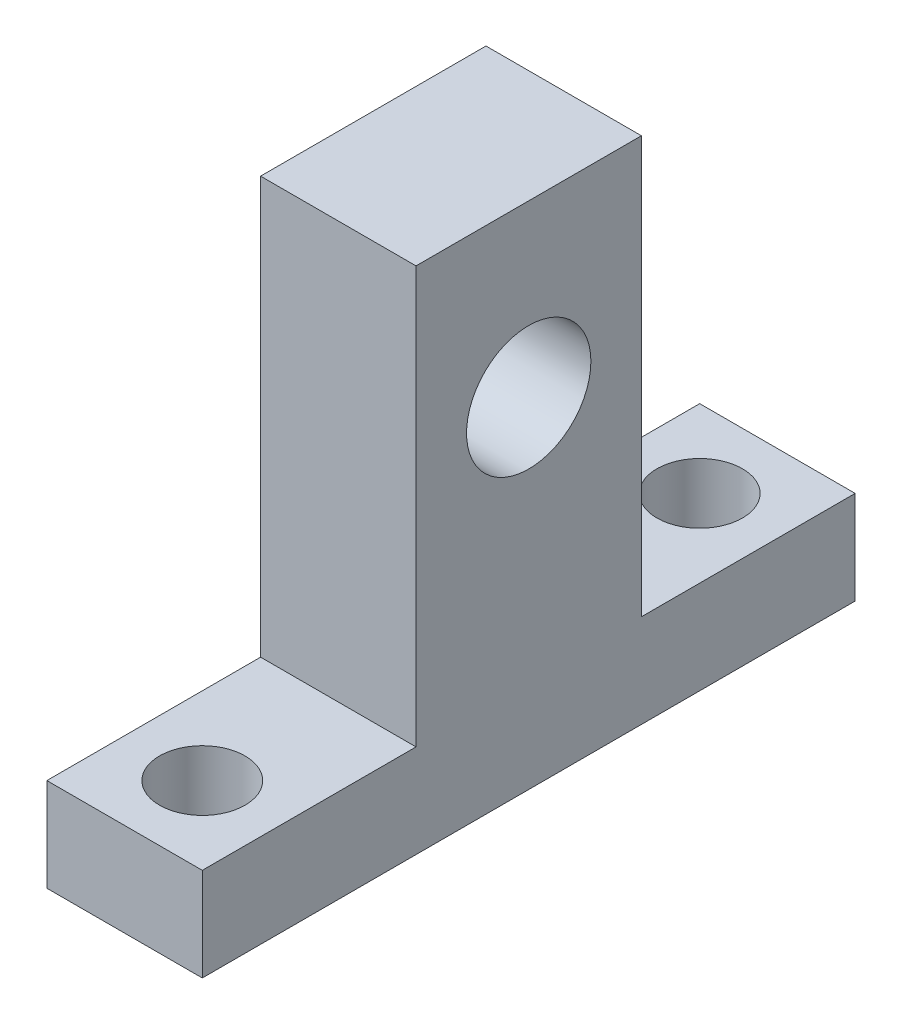
SolidWorks part; units mm, degrees
ref_plane "Front Plane" through (0, 0, 0) normal (0, 0, 1) x (1, 0, 0)
ref_plane "Top Plane" through (0, 0, 0) normal (0, 1, 0) x (1, 0, 0)
ref_plane "Right Plane" through (0, 0, 0) normal (1, 0, 0) x (0, 0, -1)
sketch "Sketch1" plane through (0, 0, 0) normal (0, 1, 0) x (1, 0, 0)
  line L1 (-5, 21) -> (5, 21)
  line L2 (-5, 21) -> (-5, -21)
  line L3 (-5, -21) -> (5, -21)
  line L4 (5, 21) -> (5, -21)
  line L5 (-5, 21) -> (5, -21) construction
  line L6 (-5, -21) -> (5, 21) construction
  line L7 (-5, 7.25) -> (5, 7.25)
  line L8 (-5, 7.25) -> (-5, -7.25)
  line L9 (-5, -7.25) -> (5, -7.25)
  line L10 (5, 7.25) -> (5, -7.25)
  line L11 (-5, 7.25) -> (5, -7.25) construction
  line L12 (-5, -7.25) -> (5, 7.25) construction
  circle A0 centre (0, 16) radius 2.75
  circle A1 centre (0, -16) radius 2.75
  point P0 (0, 0)
  point P6 (0, 0)
  dimension "D4" = 5.5
  dimension "D6" = 5.5
  dimension "D1" = 10
  dimension "D2" = 42
  dimension "D3" = 14.5
  dimension "D5" = 16
  dimension "D7" = 16
extrude "Boss-Extrude1" add sketch "Sketch1" along normal blind 6 contours L2 L7 L4 L1 A0 | L9 L2 L3 L4 A1 region at (0, 0, -20.83) region at (0, 0, 7.42)
extrude "Boss-Extrude2" add sketch "Sketch1<3>" along normal blind 32.8 contours L2 L9 L4 L7 region at (0, 0, 0)
sketch "Sketch1<3>" plane through (0, 0, 0) normal (0, 1, 0) x (1, 0, 0) same geometry as "Sketch1"
sketch "Sketch2" plane through (5, 0, 0) normal (1, 0, 0) x (0, 0, -1)
  circle A0 centre (0, 21.855) radius 4
  dimension "D1" = 8
  dimension "D2" = 21.855
extrude "Cut-Extrude1" cut sketch "Sketch2" against normal blind 32.8
